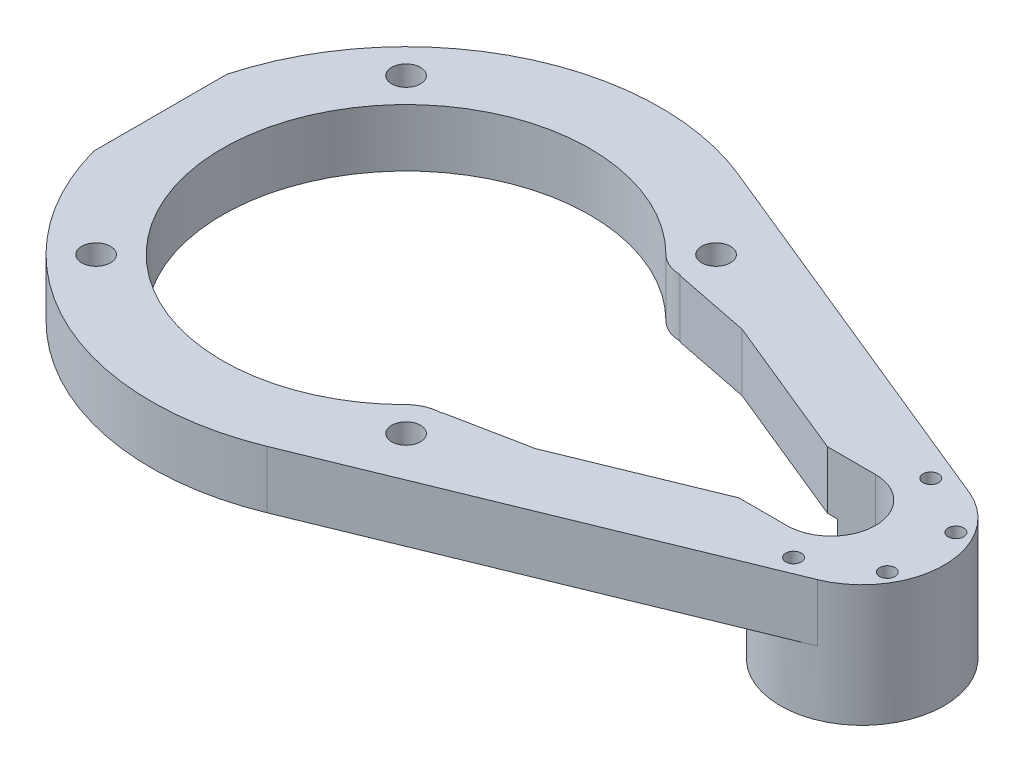
SolidWorks part; units mm, degrees
ref_plane "Front Plane" through (0, 0, 0) normal (0, 0, 1) x (1, 0, 0)
ref_plane "Top Plane" through (0, 0, 0) normal (0, 1, 0) x (1, 0, 0)
ref_plane "Right Plane" through (0, 0, 0) normal (1, 0, 0) x (0, 0, -1)
sketch "Sketch1" plane through (0, 0, 0) normal (0, 1, 0) x (1, 0, 0)
  line L0 (-75.4693, 0) -> (91.4794, 0) construction
  line L1 (35, 35) -> (-35, 35)
  line L2 (35, 35) -> (35, -35)
  line L3 (35, -35) -> (-35, -35)
  line L4 (-35, 35) -> (-35, -35)
  line L5 (35, 35) -> (-35, -35) construction
  line L6 (35, -35) -> (-35, 35) construction
  line L7 (110.0044, 17.1227) -> (21.7695, 53.217)
  line L8 (110.0044, -17.1227) -> (21.7695, -53.217)
  line L9 (86.9809, 9.254) -> (52.5473, 23.3398)
  line L10 (86.9809, -9.254) -> (52.5473, -23.3398)
  line L11 (52.5473, 23.3398) -> (33.4341, 27.1547)
  line L12 (52.5473, -23.3398) -> (33.4341, -27.1547)
  line L13 (-55.5, 15.0236) -> (-55.5, -15.0236)
  line L14 (96, 10) -> (85.1573, 10)
  line L15 (96, -10) -> (85.1573, -10)
  circle A0 centre (-35, 35) radius 3.25
  circle A1 centre (35, 35) radius 3.25
  circle A2 centre (35, -35) radius 3.25
  circle A3 centre (-35, -35) radius 3.25
  circle A4 centre (-35, 35) radius 8
  circle A5 centre (35, 35) radius 8
  circle A6 centre (35, -35) radius 8
  circle A7 centre (-35, -35) radius 8
  circle A8 centre (0, 0) radius 57.4975
  circle A9 centre (0, 0) radius 41.4975
  circle A10 centre (103, 0) radius 18.5
  circle A11 centre (96, 0) radius 10
  point P0 (0, 0)
  dimension "D2" = 6.5
  dimension "D3" = 16
  dimension "D4" = 37
  dimension "D8" = 20
  dimension "D1" = 70
  dimension "D5" = 96
  dimension "D6" = 16
  dimension "D7" = 55.5
  dimension "D9" = 7
extrude "Boss-Extrude1" add sketch "Sketch1" along normal blind 13 contours A9 L1 A5 A8 A4 | L1 A4 L4 A0 | L4 A4 L1 A0 | A9 L1 A4 | A9 L4 A4 A8 A7 | A9 A4 L4 | A9 L4 A7 | A9 A7 L3 | L3 A7 L4 A3 | A9 L3 A7 A8 A6 | L4 A7 L3 A3 | L2 A6 L3 A2 | L3 A6 L2 A2 | A9 L3 A6 | A9 A5 L1 | L1 A5 L2 A1 | L2 A5 L1 A1 | A10 L7 A8 L9 | A10 L10 A8 L8 | A10 | L11 A8 A5 L2 | A6 A8 L12 L2 region at (-31.2062, 0, -31.2062) region at (0, 0, -46.6413) region at (-29.375, 0, -35.2263) region at (-25.7994, 0, -33.5313) region at (-46.2472, 0, 0) region at (-33.5313, 0, -25.7994) region at (25.7994, 0, -33.5313) region at (68.8956, 0, -26.4915) region at (32.0251, 0, -42.182) region at (31.2062, 0, -31.2062) region at (107.2884, 0, 0) region at (45.0485, 0, -28.9885) region at (-33.5313, 0, 25.7994) region at (-42.182, 0, 32.0251) region at (0, 0, 46.6413) region at (-31.2062, 0, 31.2062) region at (-25.7994, 0, 33.5313) region at (68.8956, 0, 26.4915) region at (45.0485, 0, 28.9885) region at (31.2062, 0, 31.2062) region at (25.7994, 0, 33.5313) region at (32.0251, 0, 42.182)
sketch "Sketch2" plane through (0, 0, 0) normal (0, 1, 0) x (1, 0, 0)
  line L0 (96, -10) -> (85.1573, -10) construction
  line L1 (96, 10) -> (85.1573, 10) construction
  line L2 (96, -10) -> (85.1573, -10)
  line L3 (96, 10) -> (85.1573, 10)
  circle A0 centre (103, 0) radius 18.5
  arc A1 (110.0044, -17.1227) -> (110.0044, 17.1227) centre (103, 0) ccw construction
  arc A2 (96, -10) -> (96, 10) centre (96, 0) ccw construction
  arc A3 (96, -10) -> (96, 10) centre (96, 0) ccw
extrude "Boss-Extrude2" add sketch "Sketch2" against normal blind 14.5 contours A0 L3 region at (107.2884, 0, 0)
sketch "Sketch3" plane through (0, -14.5, 0) normal (0, -1, 0) x (1, 0, 0)
  line L0 (103, 18.5) -> (103, -18.5) construction
  line L1 (103, 0) -> (121.5, 0) construction
  line L2 (103, 0) -> (116.4234, 7.75) construction
  line L3 (103, 0) -> (103, 15.5) construction
  arc A0 (87.4356, -10) -> (87.4356, 10) centre (103, 0) ccw construction
  arc A1 (110.0044, 17.1227) -> (87.4356, 10) centre (103, 0) ccw construction
  circle A2 centre (103, 15.5) radius 1.75
  circle A3 centre (116.4234, 7.75) radius 1.75
  circle A4 centre (116.4234, -7.75) radius 1.75
  circle A5 centre (103, -15.5) radius 1.75
  circle A6 centre (89.5766, -7.75) radius 1.75 [skipped]
  circle A7 centre (89.5766, 7.75) radius 1.75 [skipped]
  point P11 (103, 0)
  point P27 (103, 0)
  dimension "D1" = 3.5
  dimension "D2" = 15.5
  dimension "D3" = 6
extrude "Cut-Extrude1" cut sketch "Sketch3" against normal up to next
